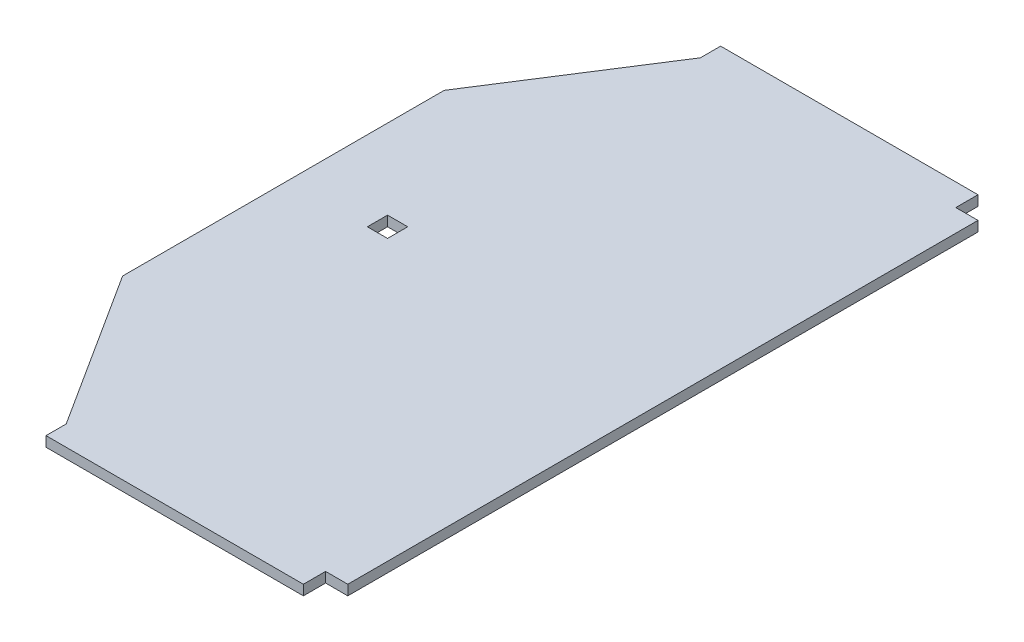
SolidWorks part; units mm, degrees
ref_plane "Front Plane" through (0, 0, 0) normal (0, 0, 1) x (1, 0, 0)
ref_plane "Top Plane" through (0, 0, 0) normal (0, 1, 0) x (1, 0, 0)
ref_plane "Right Plane" through (0, 0, 0) normal (1, 0, 0) x (0, 0, -1)
sketch "Sketch1" plane through (0, 0, 0) normal (0, 1, 0) x (1, 0, 0)
  line L1 (0, 0) -> (277, 0)
  line L3 (0, 668.38) -> (277, 668.38)
  line L4 (277, 0) -> (277, 668.38)
  line L14 (-99, 334.19) -> (-99, 493.485)
  line L18 (-99, 334.19) -> (-99, 174.895)
  line L20 (0, 668.38) -> (0, 648.38)
  line L21 (0, 648.38) -> (-99, 493.485)
  line L22 (0, 0) -> (0, 20)
  line L23 (0, 20) -> (-99, 174.895)
  point P5 (0, 658.38)
  point P7 (277, 334.19)
  dimension "D1" = 277
  dimension "D2" = 668.38
  dimension "D3" = 159.295
  dimension "D4" = 159.295
  dimension "D5" = 20
  dimension "D6" = 20
  dimension "D7" = 99
extrude "Boss-Extrude2" add sketch "Sketch1" along normal blind 10
sketch "Sketch4" plane through (0, 10, 0) normal (0, 1, 0) x (1, 0, 0)
  line L2 (0, 358.38) -> (-20, 358.38)
  line L3 (0, 358.38) -> (0, 338.38)
  line L4 (0, 338.38) -> (-20, 338.38)
  line L5 (-20, 358.38) -> (-20, 338.38)
  dimension "D2" = 20
  dimension "D3" = 20
extrude "Cut-Extrude1" cut sketch "Sketch4" against normal blind 10
sketch "Sketch5" plane through (0, 0, 0) normal (0, -1, 0) x (1, 0, 0)
  line L1 (277, -668.38) -> (255, -668.38)
  line L2 (277, -668.38) -> (277, -646.38)
  line L3 (277, -646.38) -> (255, -646.38)
  line L4 (255, -668.38) -> (255, -646.38)
  line L5 (277, 0) -> (255, 0)
  line L6 (277, 0) -> (277, -22)
  line L7 (277, -22) -> (255, -22)
  line L8 (255, 0) -> (255, -22)
  dimension "D1" = 22
  dimension "D2" = 22
  dimension "D3" = 22
  dimension "D4" = 22
extrude "Cut-Extrude2" cut sketch "Sketch5" against normal through all
